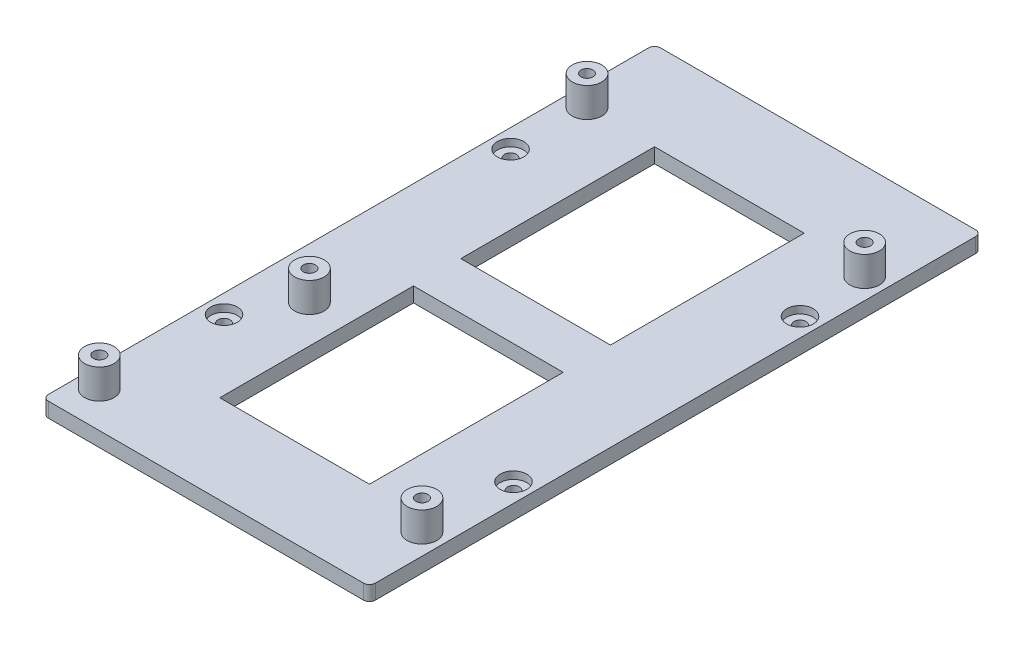
SolidWorks part; units mm, degrees
ref_plane "Plan de face" through (0, 0, 0) normal (0, 0, 1) x (1, 0, 0)
ref_plane "Plan de dessus" through (0, 0, 0) normal (0, 1, 0) x (1, 0, 0)
ref_plane "Plan de droite" through (0, 0, 0) normal (1, 0, 0) x (0, 0, -1)
sketch "Esquisse1" plane through (0, 0, 0) normal (0, 1, 0) x (1, 0, 0)
  line L0 (24.5, -24.25) -> (-24.5, 24.25)
  line L1 (27.67, -51.8) -> (-27.67, -51.8)
  line L2 (27.67, -51.8) -> (27.67, 51.8)
  line L3 (27.67, 51.8) -> (-27.67, 51.8)
  line L4 (-27.67, -51.8) -> (-27.67, 51.8)
  line L5 (27.67, -51.8) -> (-27.67, 51.8) construction
  line L6 (27.67, 51.8) -> (-27.67, -51.8) construction
  line L7 (-24.5, 24.25) -> (-24.5, -24.25)
  line L8 (-24.5, -24.25) -> (24.5, -24.25)
  line L9 (24.5, 24.25) -> (-24.5, 24.25)
  line L10 (24.5, -24.25) -> (24.5, 24.25)
  line L11 (-24.5, -24.25) -> (24.5, 24.25)
  circle A0 centre (-24.5, -24.25) radius 1.0065
  circle A1 centre (-24.5, 24.25) radius 1.0065
  circle A2 centre (24.5, 24.25) radius 1.0065
  circle A3 centre (24.5, -24.25) radius 1.0065
  point P0 (0, 0)
  dimension "D5" = 2.013
  dimension "D6" = 2.013
  dimension "D7" = 2.013
  dimension "D8" = 2.013
  dimension "D1" = 55.34
  dimension "D2" = 103.6
  dimension "D3" = 48.5
  dimension "D4" = 49
extrude "Boss.-Extru.1" add sketch "Esquisse1" against normal blind 1.25 and the other way blind 1.25 contours L4 L1 L2 L3 A3 L8 A0 L7 A1 L9 A2 L10 | A2 L9 A1 L0 L11 | A3 L10 A2 L11 L0 | A3 L0 L11 A0 L8 | A1 L7 A0 L11 L0 region at (0, 0, 16.1562) region at (16.3227, 0, 0) region at (-16.3227, 0, 0) region at (0, 0, -16.1562) region at (0, 0, 50.6255)
sketch "Esquisse2" plane through (0, 1.25, 0) normal (0, 1, 0) x (1, 0, 0)
  circle A0 centre (-24.5, 24.25) radius 2.25
  circle A1 centre (24.5, 24.25) radius 2.25
  circle A2 centre (24.5, -24.25) radius 2.25
  circle A3 centre (-24.5, -24.25) radius 2.25
extrude "Enlèv. mat.-Extru.1" cut sketch "Esquisse2" against normal blind 1.25
sketch "Esquisse4" plane through (0, 1.25, 0) normal (0, 1, 0) x (1, 0, 0)
  line L0 (27.67, 51.8) -> (-27.67, 51.8) construction
  line L2 (-27.67, -51.8) -> (-27.67, 51.8) construction
  circle A0 centre (-19.05, -15.24) radius 2.5
  circle A1 centre (-24.13, -45.72) radius 2.5
  circle A2 centre (24.13, -39.37) radius 2.5
  circle A4 centre (24.13, 35.56) radius 2.5
  circle A5 centre (-24.13, 36.83) radius 2.5
  dimension "D1" = 67.04
  dimension "D3" = 97.52
  dimension "D5" = 91.17
  dimension "D7" = 16.24
  dimension "D9" = 14.97
  dimension "D2" = 8.62
  dimension "D4" = 3.54
  dimension "D6" = 51.8
  dimension "D8" = 51.8
  dimension "D10" = 3.54
extrude "Boss.-Extru.3" add sketch "Esquisse4" along normal blind 5
sketch "Esquisse7" plane through (0, 6.25, 0) normal (0, 1, 0) x (1, 0, 0)
  circle A0 centre (-24.13, -45.72) radius 1.025
  circle A1 centre (-24.13, 36.83) radius 1.0125
  circle A2 centre (24.13, -39.37) radius 1.025
  circle A3 centre (24.13, 35.56) radius 1.025
  circle A5 centre (-19.05, -15.24) radius 1.025
extrude "Enlèv. mat.-Extru.2" cut sketch "Esquisse7" against normal blind 5
sketch "Esquisse8" plane through (0, 1.25, 0) normal (0, 1, 0) x (1, 0, 0)
  line L0 (27.67, 51.8) -> (-27.67, 51.8) construction
  line L1 (-12.67, 36.8) -> (12.67, 36.8)
  line L2 (-12.67, 36.8) -> (-12.67, -36.8)
  line L3 (-12.67, -36.8) -> (12.67, -36.8)
  line L4 (12.67, 36.8) -> (12.67, -36.8)
  line L5 (-12.67, 36.8) -> (12.67, -36.8) construction
  line L6 (-12.67, -36.8) -> (12.67, 36.8) construction
  line L7 (27.67, -51.8) -> (27.67, 51.8) construction
  point P0 (0, 0)
  dimension "D1" = 15
  dimension "D2" = 15
extrude "Enlèv. mat.-Extru.3" cut sketch "Esquisse8" against normal through all
sketch "Esquisse16" plane through (0, 1.25, 0) normal (0, 1, 0) x (1, 0, 0)
  line L0 (-12.67, 36.8) -> (-12.67, -36.8) construction
  line L1 (12.67, -4) -> (-12.67, -4)
  line L2 (12.67, -4) -> (12.67, 4)
  line L3 (12.67, 4) -> (-12.67, 4)
  line L4 (-12.67, -4) -> (-12.67, 4)
  line L5 (12.67, -4) -> (-12.67, 4) construction
  line L6 (12.67, 4) -> (-12.67, -4) construction
  point P0 (0, 0)
  dimension "D1" = 8
extrude "Boss.-Extru.6" add sketch "Esquisse16" against normal blind 2.5
fillet "Congé8" radius 1 4 edges at (27.67, 0, 51.8) (-27.67, 0, 51.8) (-27.67, 0, -51.8) (27.67, 0, -51.8)
